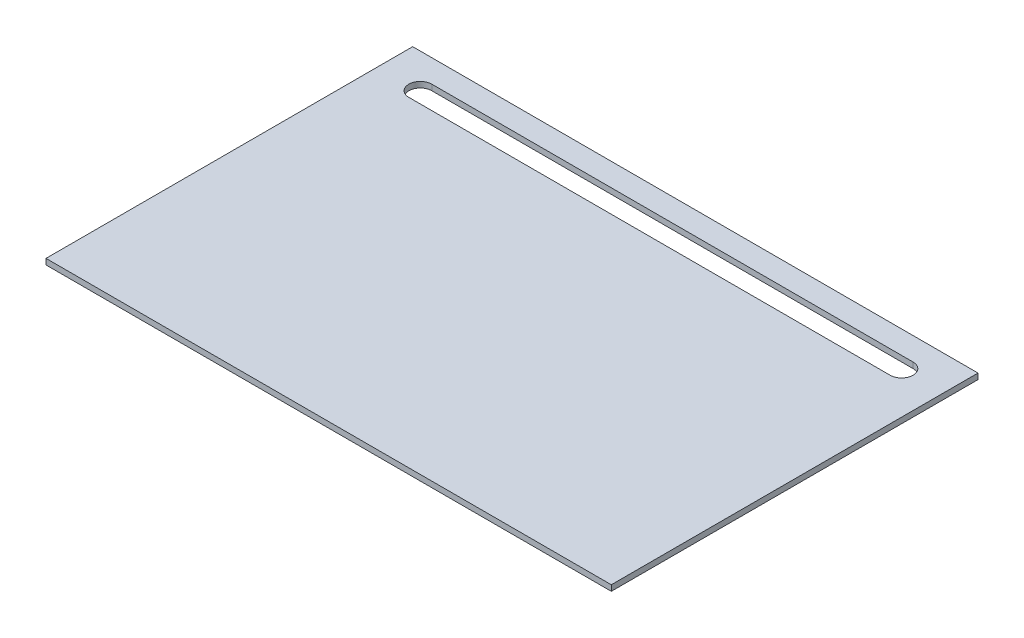
SolidWorks part; units mm, degrees
material "Maple"
ref_plane "Front Plane" through (0, 0, 0) normal (0, 0, 1) x (1, 0, 0)
ref_plane "Top Plane" through (0, 0, 0) normal (0, 1, 0) x (1, 0, 0)
ref_plane "Right Plane" through (0, 0, 0) normal (1, 0, 0) x (0, 0, -1)
sketch "Sketch1" plane through (0, 0, 0) normal (0, 1, 0) x (1, 0, 0)
  line L1 (-279.4, -152.4) -> (279.4, -152.4)
  line L2 (-279.4, -152.4) -> (-279.4, 152.4)
  line L3 (-279.4, 152.4) -> (279.4, 152.4)
  line L4 (279.4, -152.4) -> (279.4, 152.4)
  line L5 (-279.4, -152.4) -> (279.4, 152.4) construction
  line L6 (-279.4, 152.4) -> (279.4, -152.4) construction
  point P0 (0, 0)
  dimension "D1" = 304.8
  dimension "D2" = 558.8
extrude "Boss-Extrude1" add sketch "Sketch1" along normal mid plane 4.7625 contours L3 L4 L1 L2
sketch "Sketch2" plane through (0, 2.3813, 0) normal (0, 1, 0) x (1, 0, 0)
  line L0 (-279.4, -152.4) -> (-279.4, 152.4) construction
  line L1 (-279.4, 133.35) -> (-241.3, 133.35)
  line L2 (-279.4, 133.35) -> (-279.4, -133.35)
  line L3 (-279.4, -133.35) -> (-241.3, -133.35)
  line L4 (-241.3, 133.35) -> (-241.3, -133.35)
  line L5 (279.4, -152.4) -> (279.4, 152.4) construction
  line L6 (279.4, 133.35) -> (241.3, 133.35)
  line L7 (279.4, 133.35) -> (279.4, -133.35)
  line L8 (279.4, -133.35) -> (241.3, -133.35)
  line L9 (241.3, 133.35) -> (241.3, -133.35)
  line L10 (-241.3, 0) -> (241.3, 0) construction
  line L11 (-279.4, -152.4) -> (279.4, -152.4) construction
  dimension "D1" = 38.1
  dimension "D2" = 19.05
extrude "Cut-Extrude1" cut sketch "Sketch2" against normal through all
sketch "Sketch3" plane through (0, 2.3813, 0) normal (0, 1, 0) x (1, 0, 0)
  line L0 (-279.4, 152.4) -> (279.4, 152.4) construction
  line L1 (-190.5, 152.4) -> (190.5, 152.4)
  line L2 (-190.5, 152.4) -> (-190.5, 127)
  line L3 (-190.5, 127) -> (190.5, 127)
  line L4 (190.5, 152.4) -> (190.5, 127)
  line L5 (0, 0) -> (0, 127) construction
  line L6 (-241.3, -133.35) -> (-241.3, 133.35) construction
  dimension "D1" = 50.8
  dimension "D2" = 25.4
extrude "Cut-Extrude2" [suppressed] cut sketch "Sketch3" against normal through all
sketch "Sketch4" plane through (0, 2.3813, 0) normal (0, 1, 0) x (1, 0, 0)
  line L0 (-200.025, 123.825) -> (200.025, 123.825) construction
  line L1 (-200.025, 133.35) -> (200.025, 133.35)
  line L2 (-200.025, 114.3) -> (200.025, 114.3)
  line L3 (-279.4, -152.4) -> (279.4, -152.4) construction
  line L4 (-279.4, 152.4) -> (-234.95, 152.4)
  line L5 (-279.4, 152.4) -> (-279.4, -152.4)
  line L7 (0, 123.825) -> (0, 0) construction
  line L8 (-279.4, 152.4) -> (279.4, 152.4) construction
  line L9 (-279.4, -152.4) -> (-234.95, -152.4)
  line L10 (-234.95, 152.4) -> (-234.95, -152.4)
  line L12 (279.4, 152.4) -> (234.95, 152.4)
  line L13 (279.4, 152.4) -> (279.4, -152.4)
  line L14 (279.4, -152.4) -> (234.95, -152.4)
  line L15 (234.95, 152.4) -> (234.95, -152.4)
  arc A0 (-200.025, 133.35) -> (-200.025, 114.3) centre (-200.025, 123.825) ccw
  arc A1 (200.025, 114.3) -> (200.025, 133.35) centre (200.025, 123.825) ccw
  point P2 (0, 123.825)
  dimension "D1" = 25.4
  dimension "D2" = 19.05
  dimension "D3" = 19.05
  dimension "D4" = 44.45
extrude "Cut-Extrude3" cut sketch "Sketch4" against normal through all
sketch "Sketch5" [suppressed] plane through (0, 2.3813, 0) normal (0, 1, 0) x (1, 0, 0)
  line L0 (-222.25, 139.7) -> (-222.25, -139.7)
  line L1 (-279.4, 139.7) -> (279.4, 139.7) construction
  line L2 (-279.4, -139.7) -> (279.4, -139.7) construction
  line L3 (-279.4, -139.7) -> (-279.4, -120.65) construction
  dimension "D1" = 44.45
extrude "Cut-Extrude4" [suppressed] cut sketch "Sketch5" against normal through all and the other way through all
sketch "Sketch6" [suppressed] plane through (0, 2.3813, 0) normal (0, 1, 0) x (1, 0, 0)
  line L0 (-200.025, 111.125) -> (200.025, 111.125) construction
  line L1 (-200.025, 120.65) -> (200.025, 120.65)
  line L2 (-200.025, 101.6) -> (200.025, 101.6)
  line L3 (-298.45, 139.7) -> (298.45, 139.7) construction
  line L4 (298.45, -139.7) -> (298.45, 139.7) construction
  arc A0 (-200.025, 120.65) -> (-200.025, 101.6) centre (-200.025, 111.125) ccw
  arc A1 (200.025, 101.6) -> (200.025, 120.65) centre (200.025, 111.125) ccw
  point P2 (0, 111.125)
  dimension "D1" = 19.05
  dimension "D2" = 19.05
  dimension "D3" = 88.9
extrude "Cut-Extrude5" [suppressed] cut sketch "Sketch6" against normal through all
sketch "Sketch7" [suppressed] plane through (0, 2.3813, 0) normal (0, 1, 0) x (1, 0, 0)
  line L1 (-209.55, -44.45) -> (209.55, -44.45)
  line L2 (-209.55, -44.45) -> (-209.55, 44.45)
  line L3 (-209.55, 44.45) -> (209.55, 44.45)
  line L4 (209.55, -44.45) -> (209.55, 44.45)
  line L5 (-209.55, -44.45) -> (209.55, 44.45) construction
  line L6 (-209.55, 44.45) -> (209.55, -44.45) construction
  point P0 (0, 0)
  dimension "D1" = 88.9
  dimension "D2" = 469.9
extrude "Cut-Extrude6" [suppressed] cut sketch "Sketch7" against normal through all
